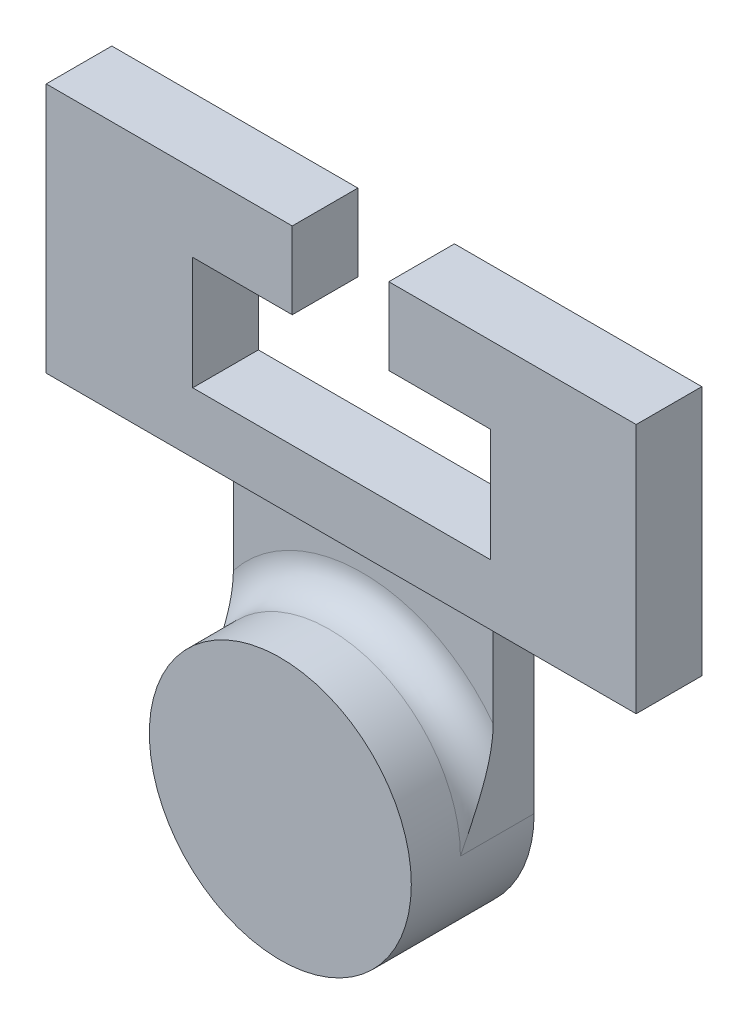
SolidWorks part; units mm, degrees
material "6061 Alloy"
ref_plane "Front Plane" through (0, 0, 0) normal (0, 0, 1) x (1, 0, 0)
ref_plane "Top Plane" through (0, 0, 0) normal (0, 1, 0) x (1, 0, 0)
ref_plane "Right Plane" through (0, 0, 0) normal (1, 0, 0) x (0, 0, -1)
sketch "Sketch1" plane through (0, 0, 0) normal (0, 0, 1) x (1, 0, 0)
  circle A0 centre (0, 0) radius 10.16
  dimension "D1" = 20.32
extrude "Boss-Extrude1" add sketch "Sketch1" against normal blind 9.525
sketch "Sketch2" plane through (0, 0, -9.525) normal (0, 0, -1) x (-1, 0, 0)
  line L1 (-10.16, 0) -> (9.9915, 0)
  line L2 (-10.16, 0) -> (-10.16, 15.7545)
  line L3 (-10.16, 15.7545) -> (9.9915, 15.7545)
  line L4 (9.9915, 0) -> (9.9915, 15.7545)
  circle A0 centre (0, 0) radius 10.16 construction
extrude "Boss-Extrude4" add sketch "Sketch2" against normal blind 3.175
sketch "Sketch3" plane through (0, 15.7545, 0) normal (0, 1, 0) x (1, 0, 0)
  line L0 (-9.9915, 9.525) -> (-22.594, 9.525)
  line L1 (-22.594, 9.525) -> (-22.594, 4.4351)
  line L2 (-22.594, 4.4351) -> (23.1661, 4.4351)
  line L3 (23.1661, 4.4351) -> (23.1661, 9.525)
  line L4 (23.1661, 9.525) -> (-9.9915, 9.525)
extrude "Boss-Extrude5" add sketch "Sketch3" along normal blind 4.699
sketch "Sketch4" plane through (0, 20.4535, 0) normal (0, 1, 0) x (1, 0, 0)
  line L0 (-22.594, 4.4351) -> (23.1661, 4.4351) construction
  line L1 (-22.594, 9.525) -> (-11.2293, 9.525)
  line L2 (-22.594, 9.525) -> (-22.594, 4.4351)
  line L3 (-22.594, 4.4351) -> (-11.2293, 4.4351)
  line L4 (-11.2293, 9.525) -> (-11.2293, 4.4351)
  line L5 (23.1661, 9.525) -> (-22.594, 9.525) construction
  line L6 (23.1661, 9.525) -> (11.852, 9.525)
  line L7 (23.1661, 9.525) -> (23.1661, 4.4351)
  line L8 (23.1661, 4.4351) -> (11.852, 4.4351)
  line L9 (11.852, 9.525) -> (11.852, 4.4351)
extrude "Boss-Extrude6" add sketch "Sketch4" along normal blind 8.763
sketch "Sketch5" plane through (0, 29.2165, 0) normal (0, 1, 0) x (1, 0, 0)
  line L0 (-11.2293, 4.4351) -> (11.852, 4.4351) construction
  line L1 (-22.594, 9.525) -> (-3.5102, 9.525)
  line L2 (-22.594, 9.525) -> (-22.594, 4.4351)
  line L3 (-22.594, 4.4351) -> (-3.5102, 4.4351)
  line L4 (-3.5102, 9.525) -> (-3.5102, 4.4351)
  line L6 (23.1661, 9.525) -> (3.9811, 9.525)
  line L7 (23.1661, 9.525) -> (23.1661, 4.4351)
  line L8 (23.1661, 4.4351) -> (3.9811, 4.4351)
  line L9 (3.9811, 9.525) -> (3.9811, 4.4351)
extrude "Boss-Extrude7" add sketch "Sketch5" along normal blind 5.969
fillet "Fillet1" radius 2.54 1 edges at (0.9251, 10.1178, -6.35)
